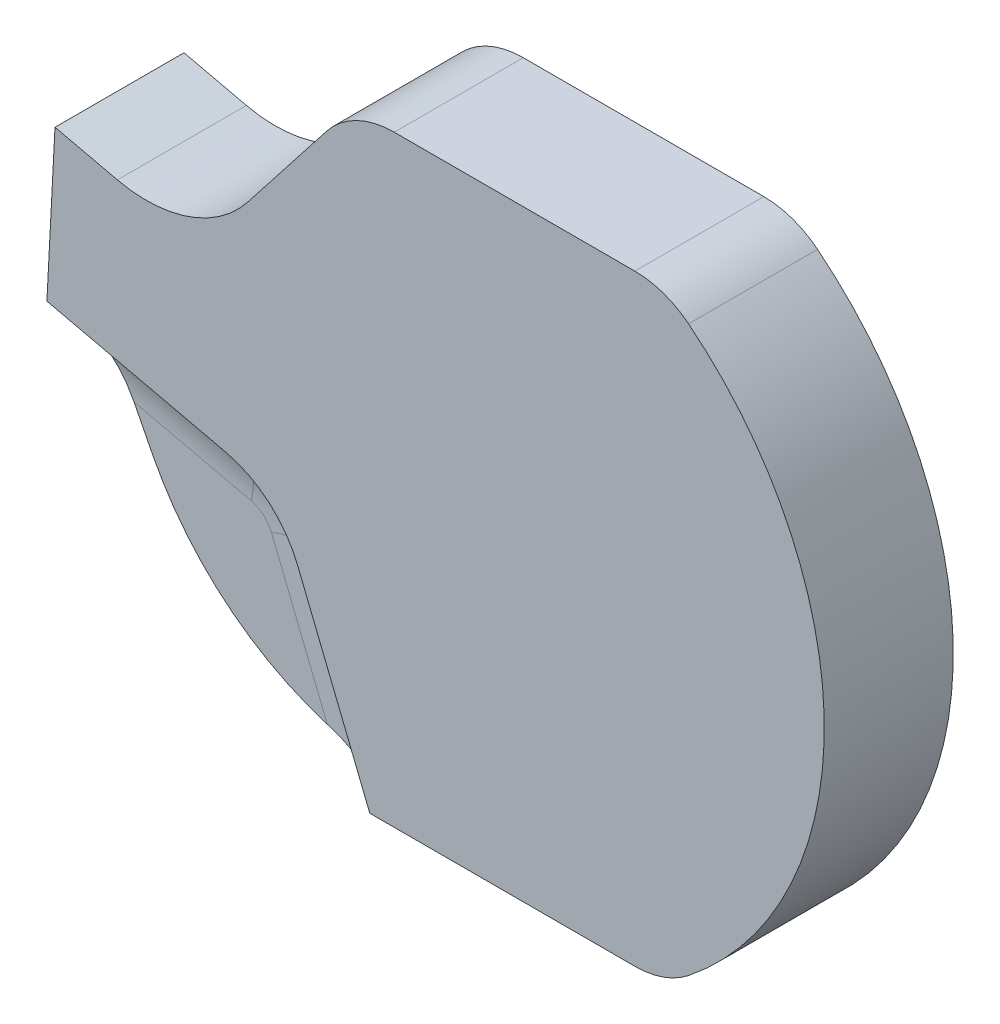
SolidWorks part; units mm, degrees
material "AISI 4340 Aço, normalizado"
ref_plane "Plano frontal" through (0, 0, 0) normal (0, 0, 1) x (1, 0, 0)
ref_plane "Plano superior" through (0, 0, 0) normal (0, 1, 0) x (1, 0, 0)
ref_plane "Plano direito" through (0, 0, 0) normal (1, 0, 0) x (0, 0, -1)
other "Center of Mass"
sketch "Sketch2" plane through (0, 0, 0) normal (0, 0, 1) x (1, 0, 0)
  line L0 (0, 0) -> (-50, 0) construction
  line L1 (-40.1946, 14.1028) -> (-47.4457, 15.7769)
  line L2 (0, 0) -> (-49.5134, 6.9587) construction
  line L5 (-8, 35) -> (19.975, 35)
  line L6 (0, 0) -> (0, 41.2714) construction
  line L8 (-15.8801, 31.1566) -> (-25.0002, 19.4835)
  line L14 (-8, -35) -> (19.975, -35)
  line L18 (-8, -35) -> (-10.8453, -35)
  line L19 (-47.4457, 15.7769) -> (-48.3883, -2.2091)
  line L20 (-48.7681, 10.0489) -> (-47.0626, 17.4363) construction
  line L22 (-48.3883, -2.2091) -> (-41.1395, -16.4357)
  circle A0 centre (0, 0) radius 50 construction
  arc A1 (26.2172, 32.8125) -> (26.2172, -32.8125) centre (0, 0) cw
  arc A5 (19.975, 35) -> (26.2172, 32.8125) centre (19.975, 25) cw
  arc A6 (-8, 35) -> (-15.8801, 31.1566) centre (-8, 25) ccw
  arc A12 (19.975, -35) -> (26.2172, -32.8125) centre (19.975, -25) ccw
  arc A17 (-41.1395, -16.4357) -> (-10.8453, -35) centre (-10.8453, -1) ccw
  arc A18 (-40.1946, 14.1028) -> (-25.0002, 19.4835) centre (-36.8203, 28.7184) ccw
  point P17 (-47.5688, 15.4017)
  point P25 (-36.3454, 12.0371)
  point P26 (-48.8323, 13.8804)
  point P27 (13.6817, -32.8125)
  point P28 (0, 0)
  point P29 (-50, 0)
  point P31 (23.2164, 35)
  point P32 (-12.8773, 35)
  dimension "D1" = 100
  dimension "D3" = 10
  dimension "D4" = 10
  dimension "D5" = 15
  dimension "D11" = 8
  dimension "D13" = 34
  dimension "D2" = 5
  dimension "D6" = 8
  dimension "D7" = 38
  dimension "D8" = 77
  dimension "D10" = 35
  dimension "D12" = 30
extrude "Boss-Extrude1" add sketch "Sketch2" along normal blind 15 contours L5 A5 A1 A12 L14 L18 A17 L22 L19 L1 A18 L8 A6
sketch "Esboço4" plane through (0, 0, 0) normal (0, 0, -1) x (-1, 0, 0)
  line L0 (48.3883, -2.2091) -> (27.6811, -6.9898)
  line L1 (19.2543, -14.1869) -> (10.8453, -35)
  line L2 (15.8801, 31.1566) -> (25.0002, 19.4835) construction
  line L3 (40.1946, 14.1028) -> (47.4457, 15.7769) construction
  line L4 (48.3883, -2.2091) -> (41.1395, -16.4357) construction
  line L5 (48.3883, -2.2091) -> (41.1395, -16.4357)
  arc A0 (10.8453, -35) -> (41.1395, -16.4357) centre (10.8453, -1) ccw construction
  arc A1 (10.8453, -35) -> (41.1395, -16.4357) centre (10.8453, -1) ccw
  arc A2 (27.6811, -6.9898) -> (19.2543, -14.1869) centre (30.3805, -18.6822) ccw
  dimension "D2" = 12
  dimension "D1" = 120
extrude "Corte-extrusão1" cut sketch "Esboço4" against normal blind 5
extrude "Corte-extrusão2" cut sketch "Esboço4<2>" along normal blind 5 from surface starting at face at (-10.886, 4.6915, 15)
sketch "Esboço4<2>" plane through (0, 0, 0) normal (0, 0, -1) x (-1, 0, 0) same geometry as "Esboço4"
fillet "Filete1" radius 10 6 edges at (-15.0498, -24.5935, 10) (-38.0347, -4.5995, 10) (-38.0347, -4.5995, 5) (-15.0498, -24.5935, 5) (-22.5871, -9.5573, 10) (-22.5871, -9.5573, 5)
other "Ponto de referência do centro da massa1"
ref_plane "Plano2" through (0, 0.026, 0) normal (0, 1, 0) x (1, 0, 0)
ref_plane "Plano3" through (1.6715, 0, 0) normal (1, 0, 0) x (0, 0, -1)
sketch "Esboço2" plane through (0, 0, 0) normal (0, 0, -1) x (-1, 0, 0)
  line L0 (8.25, 0.026) -> (-8.25, 0.026) construction
  line L1 (2.7616, 21.9428) -> (18.5218, 9.6296)
  line L2 (-11.2751, 20.2194) -> (-23.5884, 4.4591)
  line L3 (-21.8649, -9.5776) -> (-6.1047, -21.8908)
  line L4 (20.2453, -4.4071) -> (7.9321, -20.1673)
  line L5 (-5.1185, 28.0995) -> (1.7754, -28.0474) construction
  line L6 (-29.745, -3.421) -> (26.4019, 3.473) construction
  line L7 (-1.6715, 8.25) -> (-1.6715, -8.25) construction
  line L10 (-2.503, 0.026) -> (81.0211, 0.026) construction
  circle A0 centre (-1.6715, 0.026) radius 9
  arc A2 (2.7616, 21.9428) -> (-11.2751, 20.2194) centre (-3.395, 14.0627) ccw
  arc A3 (18.5218, 9.6296) -> (20.2453, -4.4071) centre (12.3652, 1.7495) cw
  arc A4 (-6.1047, -21.8908) -> (7.9321, -20.1673) centre (0.0519, -14.0107) ccw
  arc A5 (-23.5884, 4.4591) -> (-21.8649, -9.5776) centre (-15.7083, -1.6975) ccw
  dimension "D1" = 10
  dimension "D2" = 18
  dimension "D3" = 40
  dimension "D4" = 7
equation "\"escala\" = 1"
equation "\"escala_disco-arma\"= \"escala\" * 1"
equation "\"rolamento_D-ext\"= 1"
equation "\"rolamento_d-int\"= 1"
equation "\"rolamento_b-esp\"= 1"
equation "\"arma_b_rebaixo_camisa\"= 1"
equation "\"offset_altura_dente\"=20"
equation "\"disco-arma_espessura\"=15"
equation "\"D1@Boss-Extrude1\"=\"disco-arma_espessura\""
